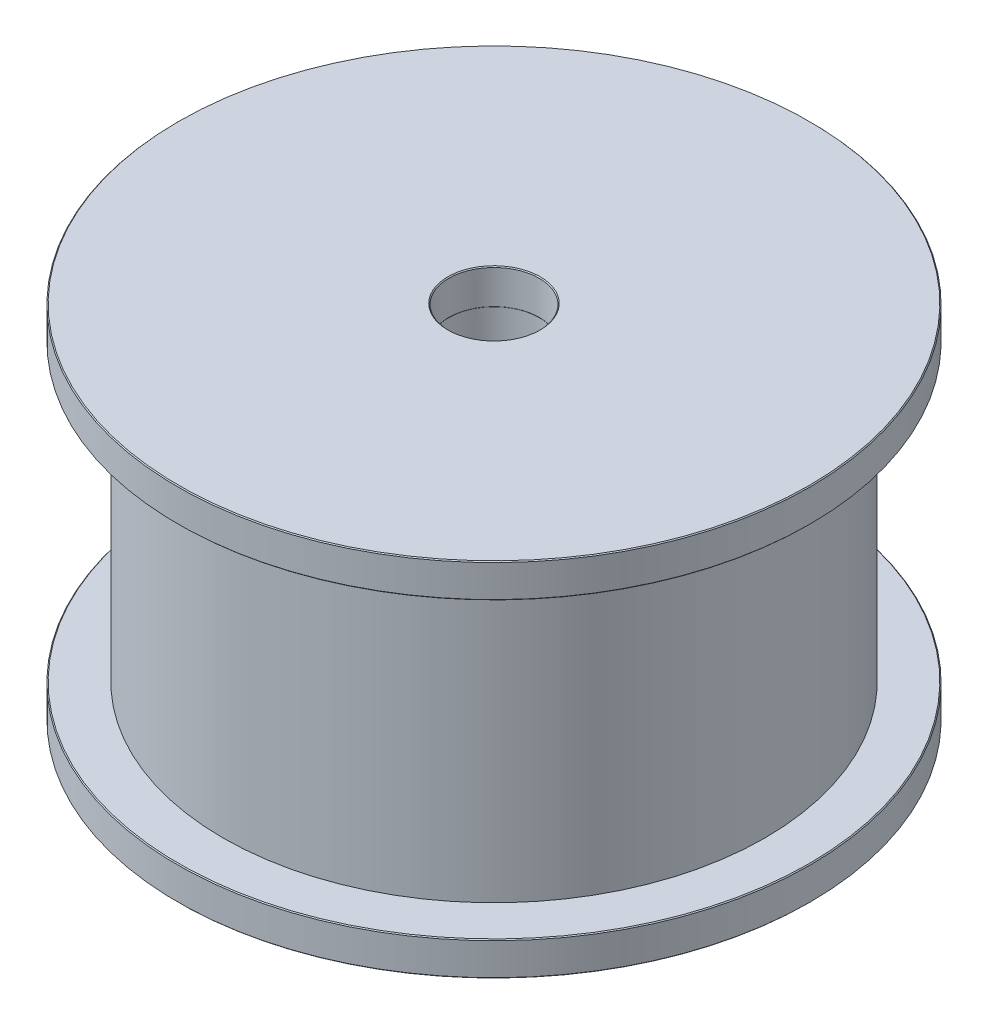
SolidWorks part; units mm, degrees
material "6061-T6 (SS)"
ref_plane "Front Plane" through (0, 0, 0) normal (0, 0, 1) x (1, 0, 0)
ref_plane "Top Plane" through (0, 0, 0) normal (0, 1, 0) x (1, 0, 0)
ref_plane "Right Plane" through (0, 0, 0) normal (1, 0, 0) x (0, 0, -1)
sketch "Sketch1" plane through (0, 0, 0) normal (0, 0, 1) x (1, 0, 0)
  line L0 (6.3627, 0) -> (44.45, 0)
  line L1 (44.45, 0) -> (44.45, 4.7625)
  line L2 (44.45, 4.7625) -> (38.1, 4.7625)
  line L3 (38.1, 4.7625) -> (38.1, 46.0375)
  line L4 (38.1, 46.0375) -> (44.45, 46.0375)
  line L5 (44.45, 46.0375) -> (44.45, 50.8)
  line L6 (44.45, 50.8) -> (6.3627, 50.8)
  line L7 (0, 50.8) -> (0, 0) construction
  line L8 (6.3627, 0) -> (6.3627, 4.7752)
  line L9 (6.3627, 4.7752) -> (6.35, 4.7752)
  line L10 (6.35, 4.7752) -> (6.35, 46.0248)
  line L11 (6.35, 46.0248) -> (6.3627, 46.0248)
  line L12 (6.3627, 46.0248) -> (6.3627, 50.8)
  line L13 (6.3627, 50.8) -> (0, 50.8) construction
  line L14 (0, 0) -> (6.3627, 0) construction
  dimension "D1" = 76.2
  dimension "D2" = 88.9
  dimension "D3" = 41.275
  dimension "D4" = 50.8
  dimension "D5" = 12.7254
  dimension "D6" = 4.7752
  dimension "D7" = 12.7
revolve "Revolve1" add sketch "Sketch1" angle 360 about L7
chamfer "Chamfer1" distance 0.127 angle 45 8 edges at (-44.45, 46.0375, 0) (-44.45, 4.7625, 0) (-6.3627, 0, 0) (-44.45, 0, 0) (-6.35, 46.0248, 0) (-6.35, 4.7752, 0) (-44.45, 50.8, 0) (-6.3627, 50.8, 0)
